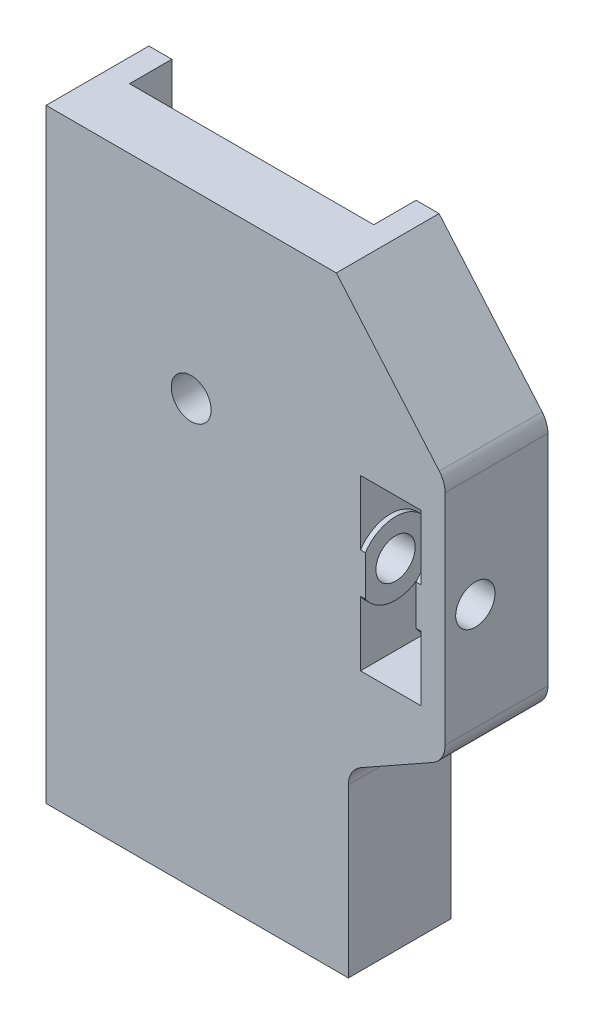
SolidWorks part; units mm, degrees
material "ABS"
ref_plane "前视基准面" through (0, 0, 0) normal (0, 0, 1) x (1, 0, 0)
ref_plane "上视基准面" through (0, 0, 0) normal (0, 1, 0) x (1, 0, 0)
ref_plane "右视基准面" through (0, 0, 0) normal (1, 0, 0) x (0, 0, -1)
other "Configuration Table"
sketch "草图1" plane through (0, 0, 0) normal (0, 0, 1) x (1, 0, 0)
  line L0 (33, 39.5) -> (24, 50)
  line L1 (24, 50) -> (0, 50)
  line L2 (0, 50) -> (0, 0)
  line L5 (33, 19.5) -> (33, 39.5)
  line L6 (26, 22.5) -> (31, 22.5)
  line L7 (26, 36.5) -> (26, 22.5)
  line L12 (31, 36.5) -> (26, 36.5)
  line L17 (31, 22.5) -> (31, 36.5)
  line L18 (0, 0) -> (25, 0)
  line L20 (25, 0) -> (33, 19.5) construction
  line L24 (0, 0) -> (25, 0)
  line L25 (33, 19.5) -> (33, 39.5)
  line L26 (33, 39.5) -> (24, 50)
  line L27 (33, 19.5) -> (25, 15)
  line L28 (25, 15) -> (25, 0)
  circle A0 centre (12, 35) radius 1.65
  dimension "D5" = 3.3
  dimension "D6" = 12
  dimension "D7" = 15
  dimension "D2" = 50
  dimension "D3" = 90
  dimension "D4" = 19.5
  dimension "D8" = 13.5
  dimension "D9" = 26
  dimension "D10" = 5
  dimension "D11" = 14
  dimension "D12" = 25
  dimension "D13" = 33
  dimension "D14" = 4.5
  dimension "D15" = 20
  dimension "D16" = 24
  dimension "D17" = 5
extrude "凸台-拉伸1" add sketch "草图1" against normal blind 8.5 contours L18 L20 L5 L0 L1 L2 A0 L17 L6 L7 L12 region at (14.1999, 25.6035, 0)
sketch "草图2" plane through (0, 50, 0) normal (0, 1, 0) x (1, 0, 0)
  line L0 (24, 8.5) -> (0, 8.5) construction
  line L1 (1.9, 8.5) -> (22.1, 8.5)
  line L2 (1.9, 8.5) -> (1.9, 5)
  line L3 (1.9, 5) -> (22.1, 5)
  line L4 (22.1, 8.5) -> (22.1, 5)
  line L5 (0, 8.5) -> (0, 0) construction
  dimension "D1" = 1.9
  dimension "D2" = 20.2
  dimension "D3" = 3.5
extrude "切除-拉伸1" cut sketch "草图2" against normal through all
sketch "草图3" plane through (33, 0, 0) normal (1, 0, 0) x (0, 0, -1)
  line L0 (0, 19.5) -> (0, 39.5) construction
  circle A0 centre (2.5, 29.5) radius 1.625
  dimension "D1" = 3.25
  dimension "D2" = 2.5
  dimension "D3" = 7
extrude "切除-拉伸2" cut sketch "草图3" against normal up to surface (7 mm away) up to face at (26, 29.5, -4.25)
sketch "草图4" plane through (26, 0, 0) normal (1, 0, 0) x (0, 0, -1)
  circle A0 centre (2.5, 29.5) radius 1
  dimension "D1" = 2
extrude "切除-拉伸3" cut sketch "草图4" against normal up to surface (3.9 mm away) up to face at (22.1, 25, -6.75)
sketch "草图5" plane through (26, 0, 0) normal (1, 0, 0) x (0, 0, -1)
  line L0 (0, 36.5) -> (0, 22.5) construction
  line L1 (0, 31.1583) -> (0, 27.8417)
  arc A0 (0, 27.8417) -> (0, 31.1583) centre (2.5, 29.5) ccw
  circle A2 centre (2.5, 29.5) radius 1 construction
  circle A3 centre (2.5, 29.5) radius 1
  dimension "D1" = 6
extrude "凸台-拉伸2" add sketch "草图5" along normal blind 0.4
sketch "草图6" plane through (31, 0, 0) normal (-1, 0, 0) x (0, 0, 1)
  line L0 (0, 22.5) -> (0, 36.5) construction
  line L1 (0, 27.8417) -> (0, 31.1583)
  circle A0 centre (-2.5, 29.5) radius 1.625 construction
  circle A1 centre (-2.5, 29.5) radius 1.625
  arc A2 (0, 31.1583) -> (0, 27.8417) centre (-2.5, 29.5) ccw
  dimension "D1" = 6
extrude "凸台-拉伸3" add sketch "草图6" along normal blind 0.4
fillet "圆角1" radius 2 3 edges at (33, 39.5, -4.25) (25, 15, -4.25) (33, 19.5, -4.25)
sketch "草图7" plane through (33, 0, 0) normal (1, 0, 0) x (0, 0, -1)
  circle A0 centre (2.5, 29.5) radius 1.625 construction
  circle A1 centre (2.5, 29.5) radius 1.625
extrude "切除-拉伸4" cut sketch "草图7" against normal through all
sketch "草图8" plane through (0, 0, -8.5) normal (0, 0, -1) x (-1, 0, 0)
  line L0 (-26, 36.5) -> (-26, 22.5) construction
  line L1 (-31, 22.5) -> (-26, 22.5)
  line L2 (-31, 22.5) -> (-31, 12.6394)
  line L3 (-31, 12.6394) -> (-26, 12.6394)
  line L4 (-26, 22.5) -> (-26, 12.6394)
  line L5 (-26, 22.5) -> (-31, 22.5) construction
extrude "切除-拉伸5" cut sketch "草图8" against normal blind 2
fillet "圆角2" radius 0.5 2 edges at (26, 15.5624, -7.5) (31, 18.375, -7.5)
fillet "圆角3" radius 1 4 edges at (31.2476, 18.7983, -6.5) (25.9472, 15.6067, -6.5) (31, 20.865, -6.5) (26, 19.1652, -6.5)
